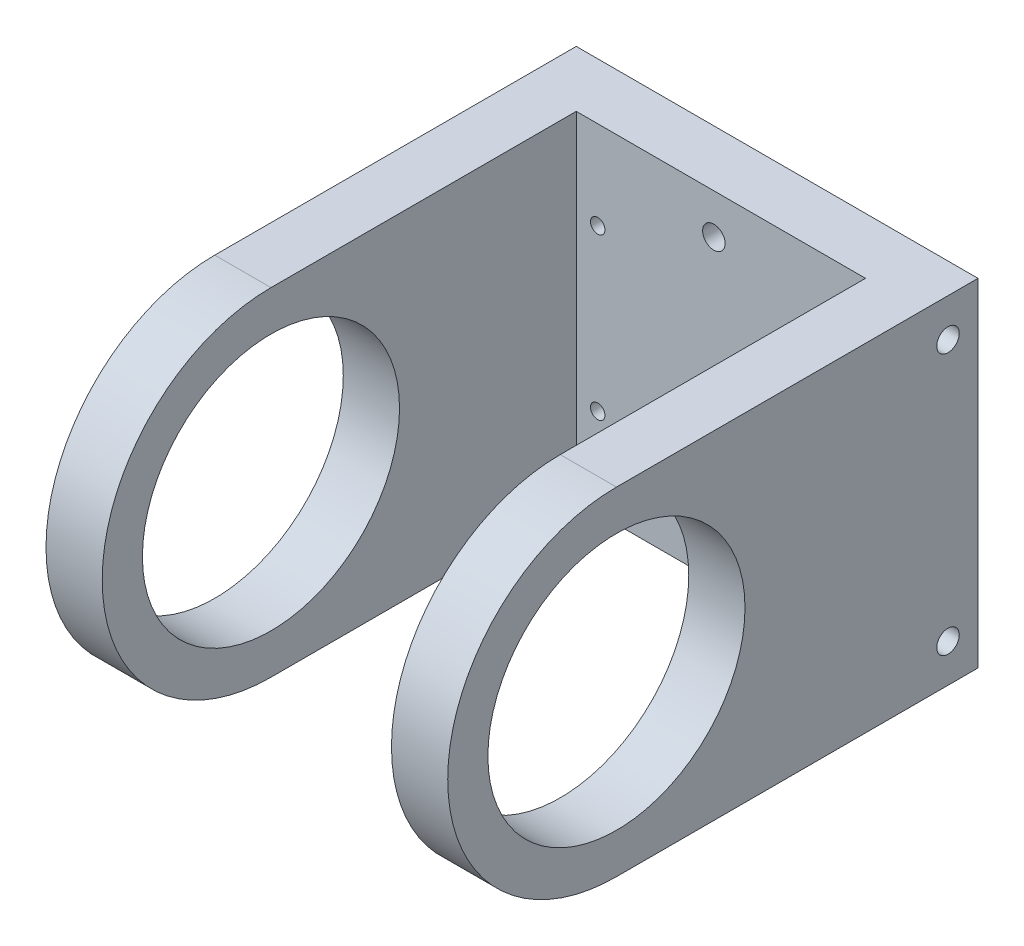
SolidWorks part; units mm, degrees
ref_plane "정면" through (0, 0, 0) normal (0, 0, 1) x (1, 0, 0)
ref_plane "윗면" through (0, 0, 0) normal (0, 1, 0) x (1, 0, 0)
ref_plane "우측면" through (0, 0, 0) normal (1, 0, 0) x (0, 0, -1)
ref_plane "평면1" through (-75, 0, 0) normal (-1, 0, 0) x (0, -1, 0)
sketch "스케치1" plane through (-75, 0, 0) normal (-1, 0, 0) x (0, -1, 0)
  line L0 (-21, 0) -> (-21, -45)
  line L1 (-21, -45) -> (21, -45)
  line L2 (21, -45) -> (21, 0)
  arc A0 (21, 0) -> (-21, 0) centre (0, 0) ccw
  dimension "D1" = 21
  dimension "D2" = 45
extrude "보스-돌출1" add sketch "스케치1" against normal blind 50
sketch "스케치2" plane through (0, 21, 0) normal (0, 1, 0) x (-1, 0, 0)
  line L0 (68, 64.1639) -> (32, 64.1639)
  line L1 (32, 64.1639) -> (32, -38)
  line L2 (32, -38) -> (68, -38)
  line L3 (68, -38) -> (68, 64.1639)
  line L4 (75, 0) -> (75, -45) construction
  line L5 (25, -45) -> (75, -45) construction
  line L6 (25, 0) -> (75, 0) construction
  circle A0 centre (50, 0) radius 21 construction
  dimension "D1" = 36
  dimension "D2" = 7
  dimension "D3" = 7
extrude "컷-돌출1" cut sketch "스케치2" against normal through all
hole_wizard "Ø1.8 (1.8) 지름 구멍1" positions "스케치4" profile "스케치3" hole size "Ø1.8" standard "Ansi Metric" end condition up to next
sketch "스케치4" plane through (0, 0, -45) normal (0, 0, -1) x (-1, 0, 0)
  point P4 (63.4618, 9.9422)
  point P5 (0, 0)
  point P12 (35.3332, 10)
  point P13 (65.3332, 10)
  point P14 (35.3332, -10)
  point P15 (65.3332, -10)
sketch "스케치3" plane through (-35.3332, 10, -45) normal (1, 0, 0) x (0, 1, 0)
  line L0 (0, 0) -> (0, 7)
  line L1 (0, 7) -> (0.9, 7)
  line L2 (0.9, 7) -> (0.9, 0)
  line L5 (0.9, 0) -> (0, 0)
  line L11 (0, -6.35) -> (0, 107.95) construction
  dimension "관통 구멍 지름" = 1.8
  dimension "관통 구멍 깊이" = 7
hole_wizard "M30 여유 구멍1" positions "스케치6" profile "스케치5" hole size "M30" standard "Ansi Metric" end condition up to next
sketch "스케치6" plane through (-25, 0, 0) normal (1, 0, 0) x (0, 0, -1)
  point P0 (0, 0)
sketch "스케치5" plane through (-25, 0, 0) normal (0, 1, 0) x (0, 0, -1)
  line L0 (0, 0) -> (0, 7)
  line L1 (0, 7) -> (16, 7)
  line L2 (16, 7) -> (16, 0)
  line L5 (16, 0) -> (0, 0)
  line L11 (0, -6.35) -> (0, 107.95) construction
  dimension "관통 구멍 지름" = 32
  dimension "관통 구멍 깊이" = 7
hole_wizard "M30 여유 구멍2" positions "스케치10" profile "스케치9" hole size "M30" standard "Ansi Metric" end condition up to next
sketch "스케치10" plane through (-75, 0, 0) normal (-1, 0, 0) x (0, 0, 1)
  point P0 (0, 0)
sketch "스케치9" plane through (-75, 0, 0) normal (0, 1, 0) x (0, 0, 1)
  line L0 (0, 0) -> (0, 7)
  line L1 (0, 7) -> (16, 7)
  line L2 (16, 7) -> (16, 0)
  line L5 (16, 0) -> (0, 0)
  line L11 (0, -6.35) -> (0, 107.95) construction
  dimension "관통 구멍 지름" = 32
  dimension "관통 구멍 깊이" = 7
sketch "스케치13" plane through (0, 0, -38) normal (0, 0, 1) x (1, 0, 0)
  line L0 (-32, -21) -> (-68, -21) construction
  line L1 (-32, 21) -> (-68, 21) construction
  circle A0 centre (-50.8768, -16) radius 1.4
  circle A1 centre (-50.8768, 16) radius 1.4
  dimension "D1" = 2.8
  dimension "D2" = 2.8
  dimension "D3" = 5
  dimension "D4" = 5
extrude "컷-돌출2" cut sketch "스케치13" against normal blind 10
sketch "스케치14" plane through (-25, 0, 0) normal (1, 0, 0) x (0, 0, -1)
  line L4 (45, -21) -> (0, -21) construction
  circle A0 centre (41.2671, 16.25) radius 1.4
  circle A1 centre (41.2671, -16.25) radius 1.4
  dimension "D1" = 2.8
  dimension "D2" = 2.8
  dimension "D4" = 4.75
  dimension "D3" = 32.5
extrude "컷-돌출3" cut sketch "스케치14" against normal blind 4
ref_plane "평면2" through (-50, 0, 0) normal (-1, 0, 0) x (0, 0, 1)
mirror "대칭 복사1" about plane through (-50, 0, 0) normal (-1, 0, 0) of "컷-돌출3"
